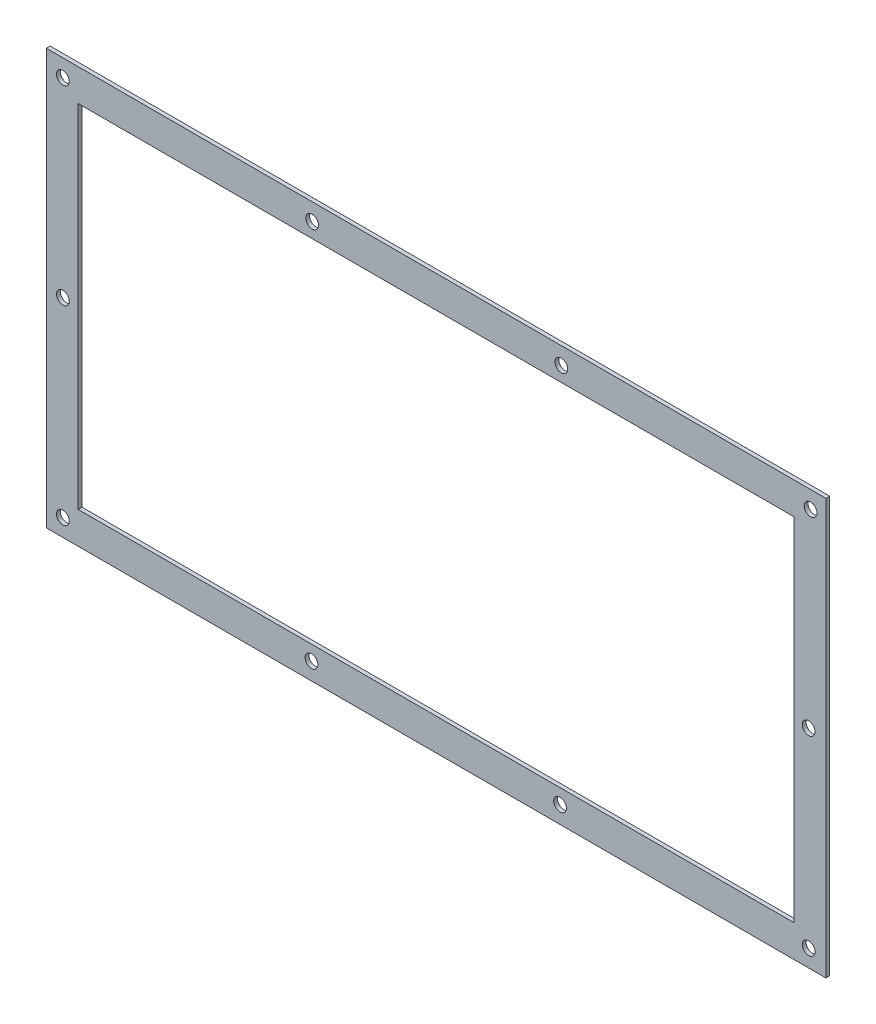
SolidWorks part; units mm, degrees
material "ASTM A36 Steel"
ref_plane "Front Plane" through (0, 0, 0) normal (0, 0, 1) x (1, 0, 0)
ref_plane "Top Plane" through (0, 0, 0) normal (0, 1, 0) x (1, 0, 0)
ref_plane "Right Plane" through (0, 0, 0) normal (1, 0, 0) x (0, 0, -1)
sketch "Sketch1" plane through (0, 0, 0) normal (0, 0, 1) x (1, 0, 0)
  line L1 (-405, -200) -> (205, -200)
  line L2 (-405, -200) -> (-405, 125)
  line L3 (-405, 125) -> (205, 125)
  line L4 (205, -200) -> (205, 125)
  line L7 (-380, -175) -> (180, -175)
  line L8 (-380, -175) -> (-380, 100)
  line L9 (-380, 100) -> (180, 100)
  line L10 (180, -175) -> (180, 100)
  point P0 (0, 0)
  point P6 (0, 0)
  dimension "D1" = 610
  dimension "D2" = 325
  dimension "D3" = 25
  dimension "D4" = 25
  dimension "D5" = 25
  dimension "D6" = 25
extrude "Boss-Extrude1" add sketch "Sketch1" along normal blind 3
sketch "Sketch2" plane through (0, 0, 3) normal (0, 0, 1) x (1, 0, 0)
  line L0 (205, 125) -> (-405, 125) construction
  line L1 (-405, 125) -> (-405, -200) construction
  circle A0 centre (-392, 111.5) radius 5
  dimension "D2" = 13
  dimension "D3" = 10
  dimension "D1" = 13.5
extrude "Cut-Extrude1" cut sketch "Sketch2" against normal blind 4
pattern_linear "LPattern1" count 4 spacing 195 along (1, 0, 0) of "Cut-Extrude1"
pattern_linear "LPattern2" count 3 spacing 149 along (0, -1, 0) of "Cut-Extrude1"
pattern_linear "LPattern3" count 4 spacing 194.5 along (1, 0, 0) of face at (-397, -186.5, 0)
pattern_linear "LPattern4" count 2 spacing 583.5 along (1, 0, 0) of face at (-397, -37.5, 0)
